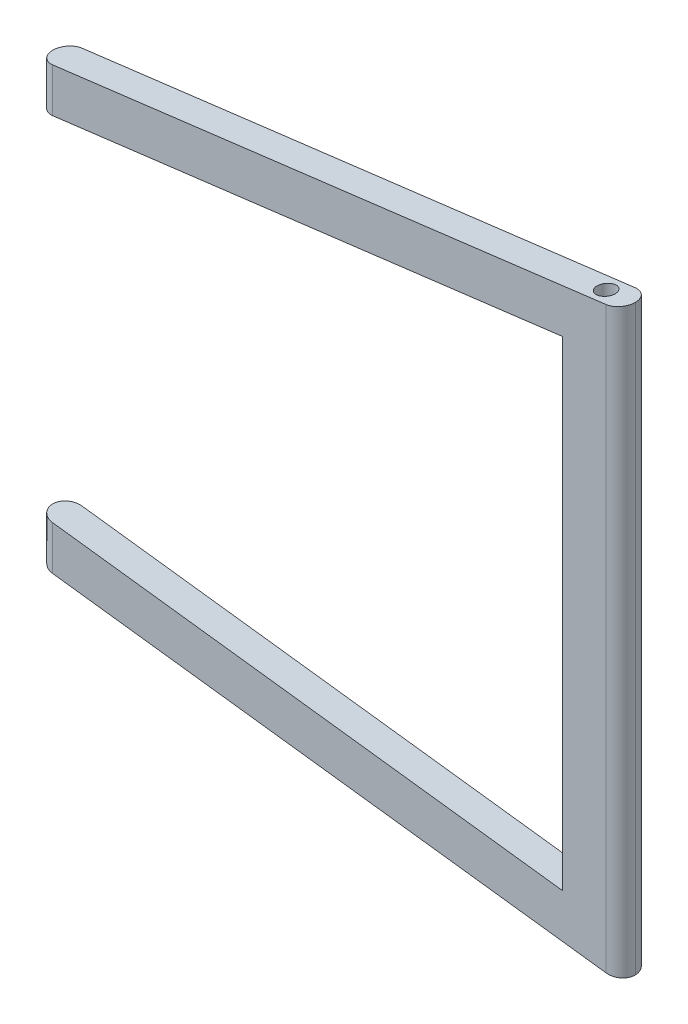
SolidWorks part; units mm, degrees
ref_plane "Plan de face" through (0, 0, 0) normal (0, 0, 1) x (1, 0, 0)
ref_plane "Plan de dessus" through (0, 0, 0) normal (0, 1, 0) x (1, 0, 0)
ref_plane "Plan de droite" through (0, 0, 0) normal (1, 0, 0) x (0, 0, -1)
sketch "Esquisse1" plane through (0, 0, 0) normal (0, 0, 1) x (1, 0, 0)
  line L0 (500, 400) -> (-1194.8227, 400) construction
  line L1 (0, 0) -> (500, 0)
  line L2 (0, 0) -> (0, 800)
  line L3 (0, 800) -> (500, 800)
  line L4 (500, 0) -> (500, 800)
  line L5 (0, 700) -> (-300, 700)
  line L6 (0, 700) -> (0, 100)
  line L7 (0, 100) -> (-300, 100)
  line L8 (-300, 700) -> (-300, 100)
  line L9 (-300, 700) -> (500, 800)
  line L10 (-300, 100) -> (500, 0)
  point P11 (-300, 400)
  dimension "D1" = 600
  dimension "D2" = 800
  dimension "D3" = 300
  dimension "D4" = 500
extrude "Boss.-Extru.1" add sketch "Esquisse1" along normal blind 40 contours L2 L0 L8 L7 | L0 L6 L5 L8 | L9 L5 L2 | L7 L10 L2 | L4 L0 L2 L10 | L0 L4 L9 L2 L6 region at (257.0621, 215.1836, 0) region at (257.0621, 584.8164, 0) region at (-150, 250, 0) region at (-150, 550, 0) region at (-100, 87.5, 0) region at (-100, 712.5, 0)
sketch "Esquisse2" plane through (0, 0, 0) normal (0, 1, 0) x (1, 0, 0)
  line L0 (-300, -20) -> (500, -20) construction
  line L4 (500, -40) -> (500, 0) construction
  circle A0 centre (460, -20) radius 12.5
  point P6 (500, -20)
  point P7 (0, 0)
  point P10 (0, 0)
  point P11 (0, 0)
  dimension "D1" = 25
  dimension "D2" = 40
extrude "Enlèv. mat.-Extru.1" cut sketch "Esquisse2" along normal through all
fillet "Congé1" radius 20 4 edges at (-300, 400, 0) (-300, 400, 40) (500, 400, 0) (500, 400, 40)
sketch "Esquisse3" plane through (0, 0, 0) normal (0, 0, 1) x (1, 0, 0)
  line L26 (-300, 100) -> (-300, 700) construction
  line L27 (-300, 100) -> (-300, 700)
  line L31 (420, 70.4669) -> (420, 729.5331)
  line L32 (-272.5579, 642.9633) -> (-292.5579, 640.4633)
  line L33 (-292.5579, 159.5367) -> (-272.5579, 157.0367)
  line L34 (-272.5579, 157.0367) -> (420, 70.4669)
  line L35 (420, 729.5331) -> (-272.5579, 642.9633)
  line L36 (420, 70.4669) -> (420, 729.5331)
  line L37 (-272.5579, 642.9633) -> (-300, 639.5331)
  line L38 (-300, 160.4669) -> (-272.5579, 157.0367)
  line L39 (-272.5579, 157.0367) -> (420, 70.4669)
  line L40 (420, 729.5331) -> (-272.5579, 642.9633)
  point P2 (-300, 639.5326)
  point P4 (-300, 160.4674)
  dimension "D1" = 60
extrude "Enlèv. mat.-Extru.4" cut sketch "Esquisse3" along normal through all contours L36 L40 L37 L27 L38 L39 region at (78.9785, 400, 0)
